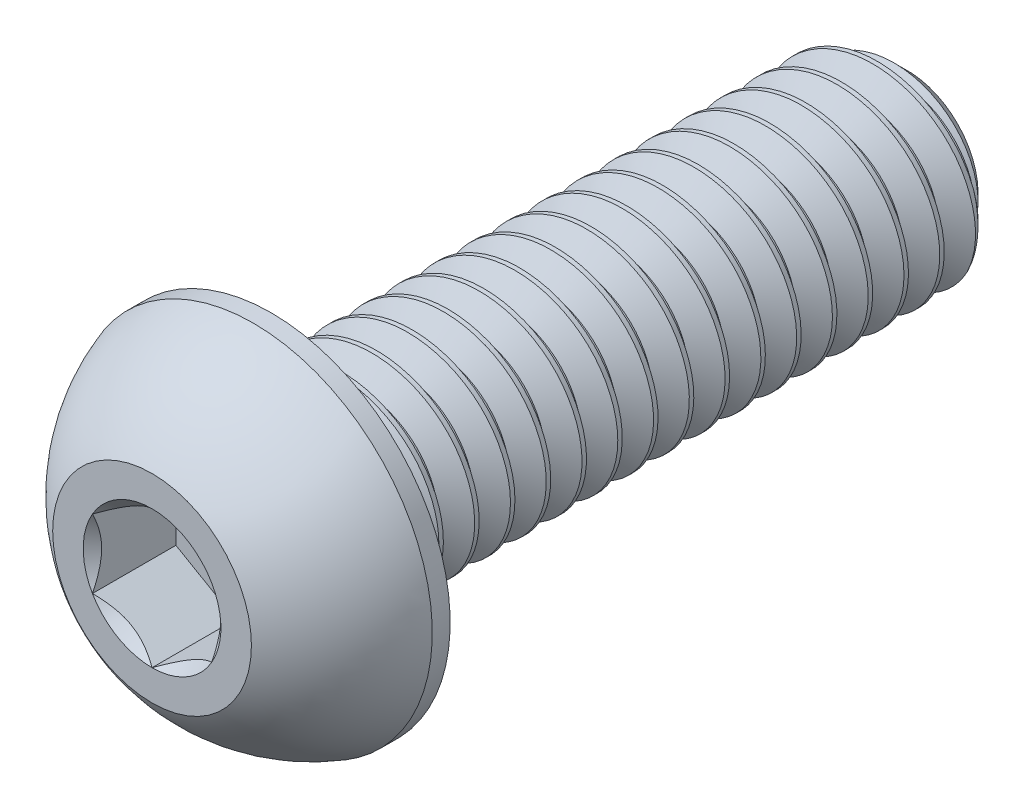
SolidWorks part; units mm, degrees
ref_plane "Front Plane" through (0, 0, 0) normal (0, 0, 1) x (1, 0, 0)
ref_plane "Top Plane" through (0, 0, 0) normal (0, 1, 0) x (1, 0, 0)
ref_plane "Right Plane" through (0, 0, 0) normal (1, 0, 0) x (0, 0, -1)
sketch "Sketch1" plane through (0, 0, 0) normal (1, 0, 0) x (0, 0, -1)
  line L0 (-4.75, 0) -> (4.75, 0) construction
  line L1 (-3.25, 2.25) -> (-3.25, -2.25) construction
  line L2 (4.75, 1.25) -> (4.75, -1.25) construction
  line L3 (4.7219, 1.2987) -> (4.9469, 0.909) construction
  line L4 (4.9469, 0.909) -> (5.1719, 1.2987) construction
  line L5 (5.1719, 1.2987) -> (4.7219, 1.2987) construction
  line L6 (4.75, 1.25) -> (5.1437, 1.25) construction
  line L7 (4.9469, 1.2987) -> (4.9469, 1.25) construction
  line L8 (4.9469, 1.25) -> (4.9469, 0.9577) construction
  line L9 (4.9469, 0.9577) -> (4.9469, 0.909) construction
  line L10 (4.9187, 0.9577) -> (4.975, 0.9577)
  line L11 (4.7359, 1.2744) -> (5.1578, 1.2744)
  line L12 (4.975, 0.9577) -> (5.1578, 1.2744)
  line L13 (4.9187, 0.9577) -> (4.7359, 1.2744)
  line L14 (-4.75, 0.75) -> (-4.75, -0.75) construction
  line L15 (4.75, 1.25) -> (-3.25, 1.25) construction
  point P3 (-3.25, 0)
  point P6 (-3.7, 0)
  point P21 (4.9469, 1.2744)
  point P24 (-3.475, 2.25)
  point P25 (3.625, -1.25)
  point P26 (-4.75, 1.25)
  dimension "Head Height" = 1.5
  dimension "Length" = 8
  dimension "Head Dia" = 4.5
  dimension "Thread Dia" = 2.5
  dimension "Pitch" = 0.45
  dimension "D2" = 0.0563
  dimension "Drive Size" = 1.5
  dimension "D1" = 1.05
  dimension "D3" = 0.225
  dimension "D4" = 1.125
sketch "Sketch2" plane through (0, 0, 0) normal (1, 0, 0) x (0, 0, -1)
  line L0 (-4.75, 0) -> (4.75, 0)
  line L1 (4.75, 0) -> (4.75, 0.89)
  line L2 (4.75, 1.25) -> (4.75, -1.25) construction
  line L3 (4.75, 0.89) -> (4.39, 1.25)
  line L4 (4.39, 1.25) -> (-3.25, 1.25)
  line L5 (-3.25, 2.25) -> (-3.25, -2.25) construction
  line L6 (-3.25, 1.25) -> (-3.25, 2.25)
  line L7 (-3.25, 2.25) -> (-3.475, 2.25)
  line L8 (4.75, 1.25) -> (5.1437, 1.25) construction
  line L9 (-4.75, 0) -> (-4.75, 1.25)
  arc A0 (-4.75, 1.25) -> (-3.475, 2.25) centre (-2.74, 0) cw
  dimension "D1" = 0.36
  dimension "D2" = 45
revolve "Revolve1" add sketch "Sketch2" angle 360 about L0
sketch "Sketch3" plane through (0, 0, 4.75) normal (0, 0, 1) x (1, 0, 0)
  line L1 (0, 0.866) -> (-0.75, 0.433)
  line L2 (-0.75, 0.433) -> (-0.75, -0.433)
  line L3 (-0.75, -0.433) -> (0, -0.866)
  line L4 (0, -0.866) -> (0.75, -0.433)
  line L5 (0.75, -0.433) -> (0.75, 0.433)
  line L6 (0.75, 0.433) -> (0, 0.866)
  circle A0 centre (0, 0) radius 0.75 construction
  dimension "D1" = 1.5
extrude "Cut-Extrude1" cut sketch "Sketch3" against normal up to vertex (1.05 mm away) up to point (0, 0, 3.7)
sketch "Sketch4" plane through (0, 0, 4.75) normal (0, 0, 1) x (1, 0, 0)
  circle A0 centre (0, 0) radius 0.866
extrude "Cut-Extrude2" cut sketch "Sketch4" against normal blind 10 draft 45
split "Split1" bodies to split 106 resulting bodies 107 108 split by face at (0, -2.25, 3.25)
sketch "Sketch5" plane through (0, 0, -4.75) normal (0, 0, -1) x (-1, 0, 0)
  circle A0 centre (0, 0) radius 1.25 construction
  circle A1 centre (0, 0) radius 1.25
curve "Helix/Spiral1" pitch 0.45 height 8.45 radius 1.25 centre (0, 0, -4.75) axis (0, 0, 1) start towards (0, 1, 0)
sketch "Sketch6" plane through (0, 0, 0) normal (1, 0, 0) x (0, 0, -1)
  line L0 (4.9187, 0.9577) -> (4.975, 0.9577) construction
  line L1 (4.9187, 0.9577) -> (4.7359, 1.2744) construction
  line L2 (4.7359, 1.2744) -> (5.1578, 1.2744) construction
  line L3 (4.975, 0.9577) -> (5.1578, 1.2744) construction
  line L4 (4.9187, 0.9577) -> (4.975, 0.9577)
  line L5 (4.9187, 0.9577) -> (4.7359, 1.2744)
  line L6 (4.7359, 1.2744) -> (5.1578, 1.2744)
  line L7 (4.975, 0.9577) -> (5.1578, 1.2744)
sweep "Cut-Sweep1" cut profiles "Sketch6" path "Helix/Spiral1" align with end faces yes
sketch "Sketch7" plane through (0, 0, 3.25) normal (0, 0, -1) x (-1, 0, 0)
  circle A1 centre (0, 0) radius 1.25
  circle A2 centre (0, 0) radius 1.25
  dimension "D1" = 0
extrude "Boss-Extrude1" add sketch "Sketch7" along normal blind 10 draft 30
equation "\"D2@Sketch1\" = \"Pitch@Sketch1\" / 8"
equation "\"D1@Sketch1\"=\"Drive Size@Sketch1\"*.7"
equation "\"D3@Sketch1\"=\"Head Height@Sketch1\"*.15"
equation "\"D1@Sketch2\"=\"Pitch@Sketch1\"*.8"
equation "\"D1@Sketch3\"=\"Drive Size@Sketch1\""
equation "\"D4@Helix/Spiral1\"=\"Pitch@Sketch1\""
equation "\"D3@Helix/Spiral1\"=\"Length@Sketch1\"+\"Pitch@Sketch1\""
equation "\"D4@Sketch1\"=\"Pitch@Sketch1\"*2.5"
